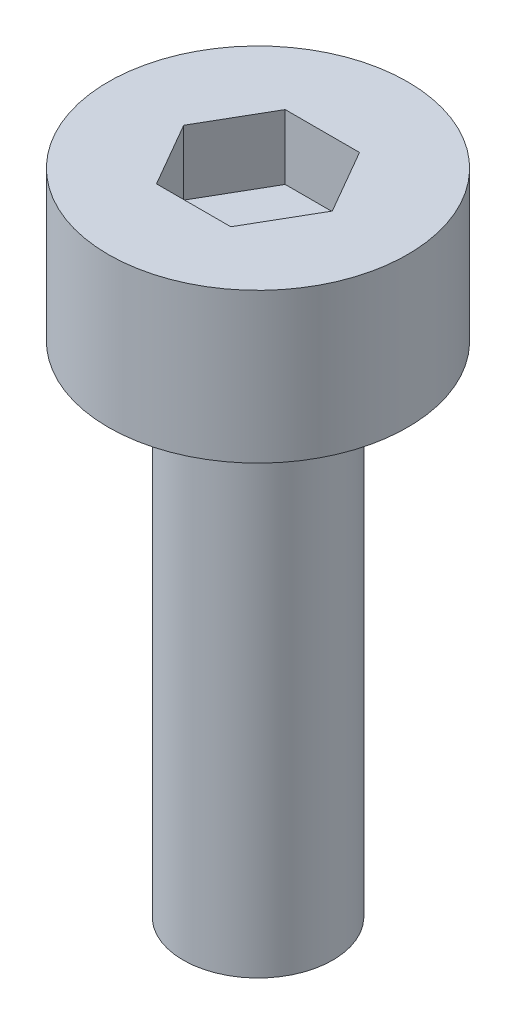
SolidWorks part; units mm, degrees
ref_plane "Front Plane" through (0, 0, 0) normal (0, 0, 1) x (1, 0, 0)
ref_plane "Top Plane" through (0, 0, 0) normal (0, 1, 0) x (1, 0, 0)
ref_plane "Right Plane" through (0, 0, 0) normal (1, 0, 0) x (0, 0, -1)
sketch "Sketch1" plane through (0, 0, 0) normal (0, 1, 0) x (1, 0, 0)
  circle A0 centre (0, 0) radius 1.5
  dimension "D1" = 3
extrude "ScrewShaft" add sketch "Sketch1" along normal blind 10
sketch "Sketch2" plane through (0, 10, 0) normal (0, 1, 0) x (1, 0, 0)
  circle A0 centre (0, 0) radius 3
  dimension "D1" = 6
extrude "Boss-Extrude2" add sketch "Sketch2" along normal blind 3
sketch "Sketch3" plane through (0, 13, 0) normal (0, 1, 0) x (1, 0, 0)
  line L0 (0, 0) -> (0, 1.29) construction
  line L1 (1.4896, 0) -> (0.7448, 1.29)
  line L2 (0.7448, 1.29) -> (-0.7448, 1.29)
  line L3 (-0.7448, 1.29) -> (-1.4896, 0)
  line L4 (-1.4896, 0) -> (-0.7448, -1.29)
  line L5 (-0.7448, -1.29) -> (0.7448, -1.29)
  line L6 (0.7448, -1.29) -> (1.4896, 0)
  circle A0 centre (0, 0) radius 1.29 construction
  dimension "D1" = 2.58
extrude "Cut-Extrude1" cut sketch "Sketch3" against normal blind 1.3
equation "\"X-ROD-SPACING\"=45"
equation "\"Y-ROD-SPACING\"=75"
equation "\"Z-ROD-SPACING\"=17.5"
equation "\"Y-BED-OFFSET\"=2"
equation "\"Y-BED-ROD-INSET\"=3.5"
equation "\"T-SLOT-NUT-FILLET-RADIUS\"=0.5"
equation "\"T-SLOT-SCREW-SHAFT-RADIUS\"=1.55"
equation "\"T-SLOT-SCREW-SHAFT-CUTOUT-LENGTH\"=11"
equation "\"T-SLOT-NUT-DEPTH\"=3.5"
equation "\"T-SLOT-NUT-WIDTH\"=2.85"
equation "\"T-SLOT-NUT-END-DISTANCE\"=8"
equation "\"ACRYLIC-THICKNESS\"=10"
equation "\"ACRYLIC-THICKNESS2\"=4.5"
equation "\"ACRYLIC-TAB-CUTOUT-SIZE\"=\"ACRYLIC-THICKNESS\"+\"ACRYLIC-TAB-TOLERANCE\"*2"
equation "\"ACRYLIC-TAB-WIDTH\"=\"ACRYLIC-THICKNESS\""
equation "\"ACRYLIC-M3-HOLE\"=2.9"
equation "\"SMOOTHROD-CAP-SCREW-DISTANCE\"=20"
equation "\"FRAME-WIDTH-INNER\"=370"
equation "\"NEMA17-HOLE-SPACING\"=31"
equation "\"NEMA17-CENTRAL-CUTOUT\"=22.5"
equation "\"Z-BRACKET-REACH\"=57"
equation "\"TOP-BRACKET-SPACING\"=40"
equation "\"SMOOTHROD-X-LENGTH\"=350"
equation "\"SMOOTHROD-Y-LENGTH\"=350"
equation "\"SMOOTHROD-Z-LENGTH\"=350"
equation "\"SMOOTHROD-TIGHTENING-HEADROOM\"=.25"
equation "\"LEADSCREW-Z-LENGTH\"=300"
equation "\"SCREW-LENGTH-FRAME\"=\"ACRYLIC-THICKNESS\" + 10"
equation "\"SCREW-HEAD-RADIUS\"=6"
equation "\"PRINTED-X-SMOOTHROD-DIAMETER\"=8.8"
equation "\"PRINTED-X-SMOOTHROD-CUTOUT\"=10"
equation "\"PRINTED-X-BASE-HEIGHT\"=10"
equation "\"PRINTED-LM8UU-CUTOUT-SIZE\"=15.5"
equation "\"PRINTED-LM8UU-CUTOUT-LENGTH\"=24.5"
equation "\"PRINTED-X-IDLER-HEIGHT\"=16"
equation "\"PSU-MOUNTING-WIDTH\"=50"
equation "\"PSU-MOUNTING-HEIGHT\"=150"
equation "\"D1@Sketch2\"=\"SCREW-HEAD-RADIUS\""
